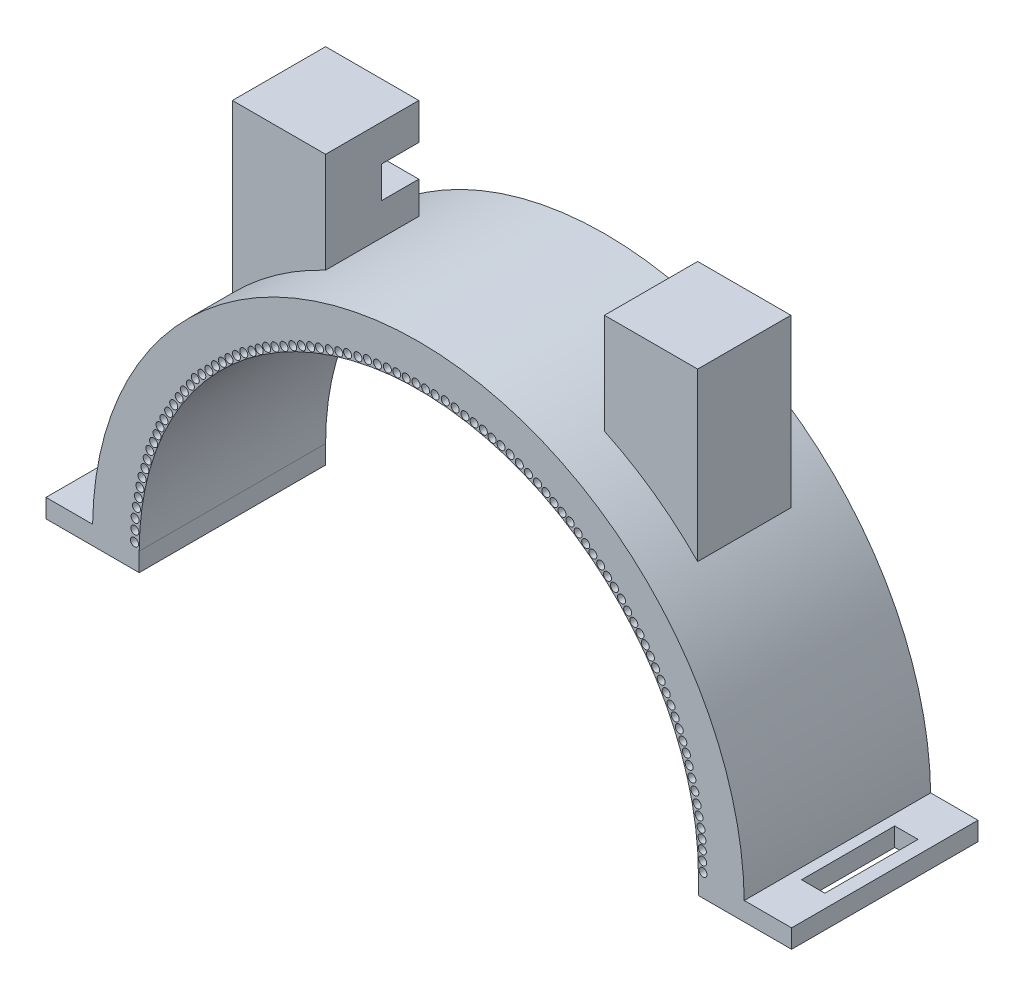
SolidWorks part; units mm, degrees
ref_plane "Front Plane" through (0, 0, 0) normal (0, 0, 1) x (1, 0, 0)
ref_plane "Top Plane" through (0, 0, 0) normal (0, 1, 0) x (1, 0, 0)
ref_plane "Right Plane" through (0, 0, 0) normal (1, 0, 0) x (0, 0, -1)
sketch "Sketch1" plane through (0, 0, 0) normal (0, 0, 1) x (1, 0, 0)
  line L0 (-44.6875, 2.1195) -> (-39.6875, 2.1195)
  line L1 (20.3125, 2.1195) -> (25.2325, 2.1195)
  arc A0 (-44.6875, 2.1195) -> (25.2325, 2.1195) centre (-9.7275, 1.6278) cw
  arc A1 (-39.6875, 2.1195) -> (20.3125, 2.1195) centre (-9.6875, 2.1195) cw
  dimension "D3" = 30
  dimension "D4" = 30
  dimension "D1" = 60
  dimension "D2" = 5
extrude "Boss-Extrude1" add sketch "Sketch1" along normal blind 20
sketch "Sketch2" plane through (0, 0, 20) normal (0, 0, 1) x (1, 0, 0)
  line L0 (20.3125, 2.1195) -> (20.3125, 0.1195)
  line L1 (20.3125, 2.1195) -> (30.3125, 2.1195)
  line L2 (20.3125, 0.1195) -> (30.3125, 0.1195)
  line L3 (30.3125, 2.1195) -> (30.3125, 0.1195)
  line L4 (-39.6875, 2.1195) -> (-39.6875, 0.1195)
  line L5 (-39.6875, 2.1195) -> (-49.6875, 2.1195)
  line L6 (-39.6875, 0.1195) -> (-49.6875, 0.1195)
  line L7 (-49.6875, 2.1195) -> (-49.6875, 0.1195)
extrude "Boss-Extrude2" add sketch "Sketch2" against normal blind 20
sketch "Sketch3" plane through (0, 2.1195, 0) normal (0, 1, 0) x (1, 0, 0)
  line L0 (-48.4375, -5) -> (-45.9375, -5)
  line L1 (-48.4375, -5) -> (-48.4375, -15)
  line L2 (-45.9375, -5) -> (-45.9375, -15)
  line L3 (-48.4375, -15) -> (-45.9375, -15)
  line L4 (26.3784, -5) -> (28.8784, -5)
  line L5 (26.3784, -5) -> (26.3784, -15)
  line L6 (28.8784, -5) -> (28.8784, -15)
  line L7 (26.3784, -15) -> (28.8784, -15)
  line L8 (-44.6875, -20) -> (-49.6875, -20) construction
  line L9 (-44.6875, 0) -> (-49.6875, 0) construction
  line L10 (-49.6875, 0) -> (-49.6875, -20) construction
  line L11 (-44.6875, -20) -> (-44.6875, 0) construction
  line L12 (30.3125, -20) -> (25.2325, -20) construction
  line L13 (30.3125, 0) -> (25.2325, 0) construction
  point P20 (27.7725, 0)
  dimension "D1" = 10
  dimension "D2" = 5
  dimension "D3" = 5
  dimension "D4" = 1.25
  dimension "D5" = 1.25
  dimension "D6" = 2.5
  dimension "D7" = 2.5
  dimension "D8" = 10
  dimension "D9" = 5
  dimension "D10" = 5
extrude "Cut-Extrude1" cut sketch "Sketch3" against normal through all
sketch "Sketch5" plane through (0, 0, 0) normal (0, 1, 0) x (1, 0, 0)
  line L0 (-34.6875, -5) -> (-34.6875, -15)
  line L1 (-34.6875, -5) -> (-24.6875, -5)
  line L2 (-34.6875, -15) -> (-24.6875, -15)
  line L3 (-24.6875, -5) -> (-24.6875, -15)
  line L4 (5.2325, -5) -> (5.2325, -15)
  line L5 (5.2325, -5) -> (15.2325, -5)
  line L6 (5.2325, -15) -> (15.2325, -15)
  line L7 (15.2325, -5) -> (15.2325, -15)
  line L8 (25.2325, -20) -> (25.2325, 0) construction
  line L11 (-44.6875, -20) -> (-44.6875, 0) construction
  line L12 (-44.6875, -20) -> (25.2325, -20) construction
  line L13 (25.2325, 0) -> (-44.6875, 0) construction
  dimension "D1" = 10
  dimension "D2" = 10
  dimension "D3" = 10
  dimension "D4" = 10
  dimension "D5" = 10
  dimension "D6" = 10
  dimension "D7" = 5
  dimension "D8" = 5
extrude "Boss-Extrude3" add sketch "Sketch5" against normal up to surface and the other way blind 15 from offset 29 up to face at (-9.7275, 19.3554, 10)
sketch "Sketch15" plane through (0, 0, 5) normal (0, 0, -1) x (-1, 0, 0)
  line L0 (-5.2325, 40.0931) -> (-5.2325, 36.6071)
  line L1 (-5.2325, 40.0931) -> (-15.19, 40.0931)
  line L2 (-5.2325, 36.6071) -> (-15.19, 36.6071)
  line L3 (-15.19, 40.0931) -> (-15.19, 36.6071)
  line L4 (-5.2325, 44) -> (-5.2325, 33.2291) construction
  line L5 (24.6875, 40.0931) -> (34.6875, 40.0931)
  line L6 (24.6875, 40.0931) -> (24.6875, 36.6863)
  line L7 (34.6875, 40.0931) -> (34.6875, 36.6863)
  line L8 (24.6875, 36.6863) -> (34.6875, 36.6863)
  line L11 (24.6875, 44) -> (24.6875, 33.2291) construction
  line L12 (34.6875, 44) -> (34.6875, 26.1113) construction
extrude "Cut-Extrude2" cut sketch "Sketch15" against normal blind 4
sketch "Sketch16" plane through (0, 0, 0) normal (0, 0, 1) x (1, 0, 0)
  circle A0 centre (-40.1941, 2.7079) radius 0.43
extrude "Cut-Extrude3" cut sketch "Sketch16" along normal through all
sketch "Sketch19" plane through (0, 0, 0) normal (0, 0, -1) x (-1, 0, 0)
  circle A0 centre (40.1578, 3.8426) radius 0.43
  circle A1 centre (40.13, 4.9515) radius 0.43
  circle A2 centre (39.9767, 6.0417) radius 0.43
  circle A3 centre (39.7796, 7.0606) radius 0.43
  circle A4 centre (39.6116, 8.0836) radius 0.43
  circle A5 centre (39.3841, 9.1172) radius 0.43
  circle A6 centre (38.8298, 11.0432) radius 0.43
  circle A7 centre (38.552, 12.049) radius 0.43
  circle A8 centre (39.0888, 10.095) radius 0.43
  circle A9 centre (38.1412, 12.9835) radius 0.43
  circle A10 centre (37.7688, 13.8951) radius 0.43
  circle A11 centre (37.4489, 14.8) radius 0.43
  circle A12 centre (37.0322, 15.6704) radius 0.43
  circle A13 centre (36.5284, 16.6098) radius 0.43
  circle A14 centre (35.9862, 17.5777) radius 0.43
  circle A15 centre (35.3936, 18.5255) radius 0.43
  circle A16 centre (34.8439, 19.4129) radius 0.43
  circle A17 centre (34.1954, 20.2966) radius 0.43
  circle A18 centre (33.6716, 21.1637) radius 0.43
  circle A19 centre (30.0499, 24.8223) radius 0.43
  circle A20 centre (29.2478, 25.5289) radius 0.43
  circle A21 centre (28.4683, 26.171) radius 0.43
  circle A22 centre (27.5753, 26.7528) radius 0.43
  circle A23 centre (26.808, 27.3214) radius 0.43
  circle A24 centre (26.0182, 27.8991) radius 0.43
  circle A25 centre (25.1171, 28.3883) radius 0.43
  circle A26 centre (24.1527, 28.9169) radius 0.43
  circle A27 centre (23.2134, 29.4527) radius 0.43
  circle A28 centre (22.266, 29.9151) radius 0.43
  circle A29 centre (21.2921, 30.3178) radius 0.43
  circle A30 centre (20.3412, 30.6707) radius 0.43
  circle A31 centre (19.2944, 31.0272) radius 0.43
  circle A32 centre (18.2733, 31.3465) radius 0.43
  circle A33 centre (17.3307, 31.6591) radius 0.43
  circle A34 centre (16.2138, 31.9251) radius 0.43
  circle A35 centre (15.1964, 32.1633) radius 0.43
  circle A36 centre (14.1189, 32.2761) radius 0.43
  circle A66 centre (9.9893, 32.5866) radius 0.43
  circle A67 centre (32.9721, 21.9118) radius 0.43
  circle A68 centre (32.2147, 22.6535) radius 0.43
  circle A69 centre (31.5046, 23.4424) radius 0.43
  circle A70 centre (30.7688, 24.1392) radius 0.43
  circle A71 centre (13.0587, 32.4462) radius 0.43
  circle A72 centre (12.0539, 32.5016) radius 0.43
  circle A73 centre (11.0343, 32.5356) radius 0.43
  circle A74 centre (8.9613, 32.5526) radius 0.43
  circle A75 centre (7.9418, 32.5186) radius 0.43
  circle A76 centre (6.8373, 32.5186) radius 0.43
  circle A77 centre (5.7801, 32.3784) radius 0.43
  circle A78 centre (4.7315, 32.1802) radius 0.43
  circle A79 centre (3.749, 32.0151) radius 0.43
  circle A81 centre (2.7582, 31.8252) radius 0.43
  circle A82 centre (1.8252, 31.5445) radius 0.43
  circle A83 centre (0.8592, 31.3381) radius 0.43
  circle A84 centre (-0.1151, 31.0161) radius 0.43
  circle A85 centre (-1.0976, 30.6362) radius 0.43
  circle A86 centre (-2.0761, 30.2223) radius 0.43
  circle A87 centre (-3.05, 29.8181) radius 0.43
  circle A88 centre (-3.9503, 29.3863) radius 0.43
  circle A89 centre (-4.8139, 28.8902) radius 0.43
  circle A90 centre (-5.6775, 28.4125) radius 0.43
  circle A91 centre (-6.5503, 27.9623) radius 0.43
  circle A92 centre (-7.4135, 27.3661) radius 0.43
  circle A93 centre (-8.22, 26.7775) radius 0.43
  circle A94 centre (-8.9869, 26.1963) radius 0.43
  circle A95 centre (-9.8318, 25.5971) radius 0.43
  circle A96 centre (-10.5531, 24.9033) radius 0.43
  circle A97 centre (-11.3102, 24.2581) radius 0.43
  circle A98 centre (-12.0642, 23.5574) radius 0.43
  circle A99 centre (-12.7268, 22.7729) radius 0.43
  circle A100 centre (-13.3819, 22.0417) radius 0.43
  circle A101 centre (-14.0453, 21.3254) radius 0.43
  circle A102 centre (-14.6106, 20.5751) radius 0.43
  circle A103 centre (-15.161, 19.7939) radius 0.43
  circle A104 centre (-15.7224, 18.9794) radius 0.43
  circle A105 centre (-16.3234, 18.1412) radius 0.43
  circle A106 centre (-16.8612, 17.2476) radius 0.43
  circle A107 centre (-17.3701, 16.3491) radius 0.43
  circle A108 centre (-17.8225, 15.4728) radius 0.43
  circle A109 centre (-18.2593, 14.59) radius 0.43
  circle A110 centre (-18.6414, 13.6451) radius 0.43
  circle A111 centre (-19.0307, 12.7126) radius 0.43
  circle A112 centre (-19.3164, 11.7264) radius 0.43
  circle A113 centre (-19.6114, 10.6849) radius 0.43
  circle A114 centre (-19.9269, 9.6352) radius 0.43
  circle A115 centre (-20.1751, 8.5643) radius 0.43
  circle A116 centre (-20.384, 7.5455) radius 0.43
  circle A117 centre (-20.593, 6.5268) radius 0.43
  circle A118 centre (-20.6975, 5.5734) radius 0.43
  circle A119 centre (-20.7367, 4.5808) radius 0.43
  circle A120 centre (-20.7678, 3.5584) radius 0.43
  circle A121 centre (-20.8089, 2.5218) radius 0.43
  point P74 (0, 0)
  point P76 (0, 0)
  point P90 (6.8373, 32.5186)
  point P132 (35.9862, 17.5777)
  point P166 (-18.2751, 15.6704)
extrude "Cut-Extrude4" cut sketch "Sketch19" against normal through all
